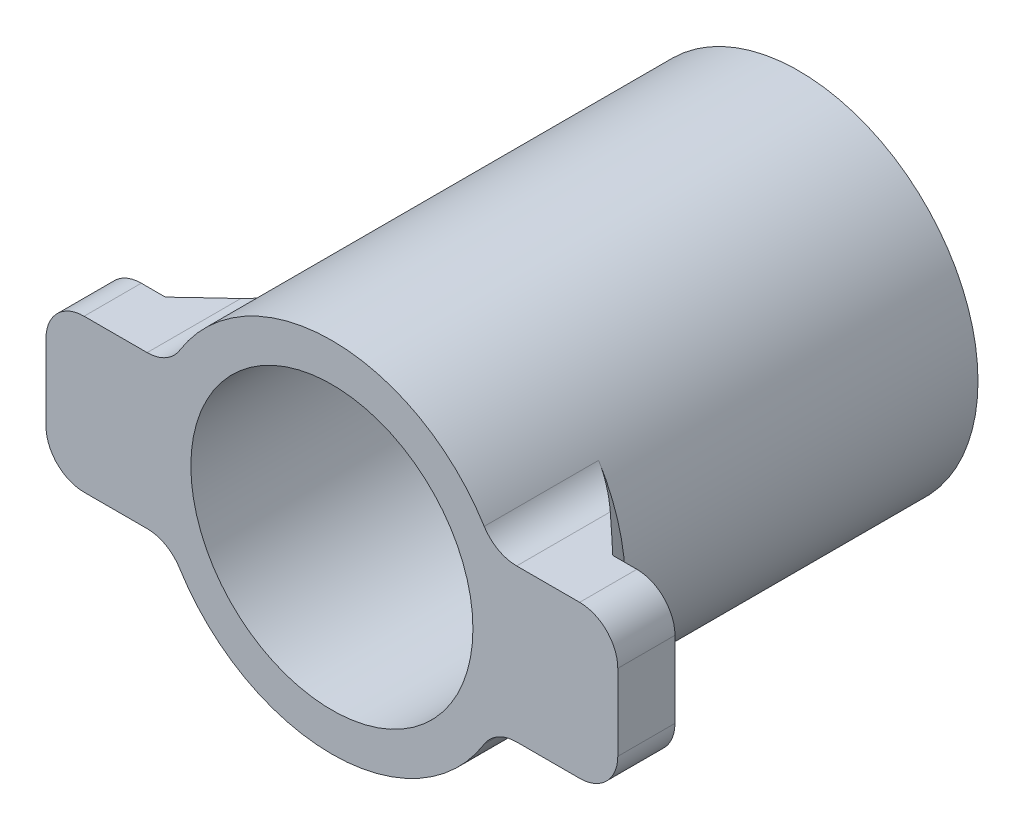
SolidWorks part; units mm, degrees
ref_plane "前视基准面" through (0, 0, 0) normal (0, 0, 1) x (1, 0, 0)
ref_plane "上视基准面" through (0, 0, 0) normal (0, 1, 0) x (1, 0, 0)
ref_plane "右视基准面" through (0, 0, 0) normal (1, 0, 0) x (0, 0, -1)
sketch "草图1" plane through (0, 0, 0) normal (0, 0, 1) x (1, 0, 0)
  circle A0 centre (0, 0) radius 7.4
  circle A1 centre (0, 0) radius 9.4
  dimension "D1" = 14.8
  dimension "D2" = 2
extrude "凸台-拉伸1" add sketch "草图1" along normal blind 24.5
sketch "草图2" plane through (0, 0, 24.5) normal (0, 0, 1) x (1, 0, 0)
  line L0 (6.2258, 4) -> (15, 4)
  line L1 (-15, -4) -> (-6.2258, -4)
  line L2 (-15, -4) -> (-15, 4)
  line L3 (-15, 4) -> (-6.2258, 4)
  line L4 (15, -4) -> (15, 4)
  line L5 (-15, -4) -> (0, 0) construction
  line L6 (-15, 4) -> (0, 0) construction
  line L7 (7.1501, 1.9067) -> (15, 4) construction
  line L8 (7.1501, -1.9067) -> (15, -4) construction
  line L9 (6.2258, -4) -> (15, -4)
  circle A0 centre (0, 0) radius 7.4 construction
  arc A1 (6.2258, -4) -> (6.2258, 4) centre (0, 0) ccw
  arc A3 (-6.2258, 4) -> (-6.2258, -4) centre (0, 0) ccw
  dimension "D1" = 8
  dimension "D2" = 30
extrude "凸台-拉伸2" add sketch "草图2" against normal blind 3
fillet "圆角1" radius 2 8 edges at (-8.5065, 4, 23) (-8.5065, -4, 23) (8.5065, -4, 23) (8.5065, 4, 23) (15, 4, 23) (-15, 4, 23) (-15, -4, 23) (15, -4, 23)
chamfer "倒角1" distance 3 angle 45 2 edges at (-9.4, 0, 21.5) (9.4, 0, 21.5)
